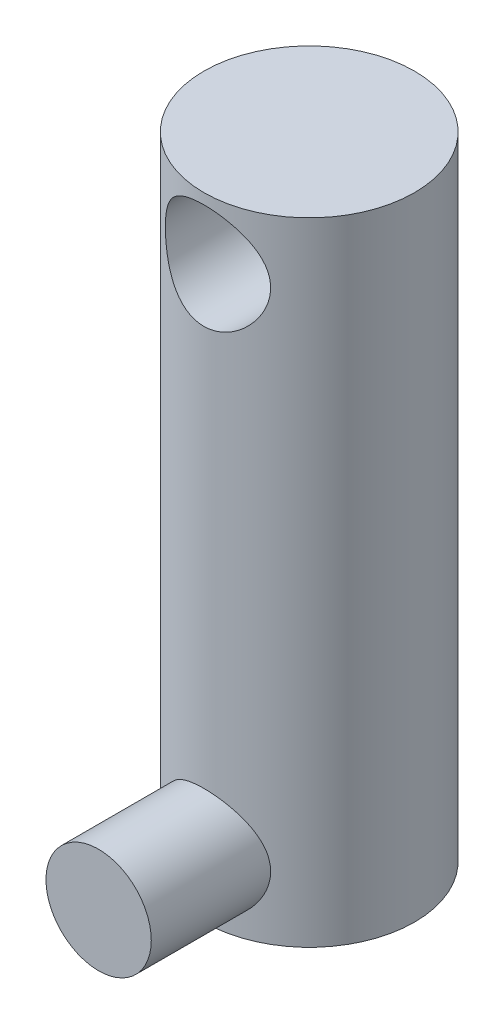
SolidWorks part; units mm, degrees
ref_plane "Front Plane" through (0, 0, 0) normal (0, 0, 1) x (1, 0, 0)
ref_plane "Top Plane" through (0, 0, 0) normal (0, 1, 0) x (1, 0, 0)
ref_plane "Right Plane" through (0, 0, 0) normal (1, 0, 0) x (0, 0, -1)
sketch "Sketch1" plane through (0, 0, 0) normal (0, 1, 0) x (1, 0, 0)
  circle A0 centre (0, 0) radius 5
  dimension "D1" = 10
extrude "Boss-Extrude1" add sketch "Sketch1" along normal blind 30
ref_plane "Plane1" through (0, 0, 5) normal (0, 0, 1) x (1, 0, 0)
sketch "Sketch2" plane through (0, 0, 5) normal (0, 0, 1) x (1, 0, 0)
  circle A0 centre (0, 3) radius 2.5
  point P2 (0, 0)
  point P8 (0, 0)
  point P9 (0, 25.9624)
  dimension "D1" = 5
  dimension "D2" = 3
extrude "Boss-Extrude2" add sketch "Sketch2" along normal blind 5 and the other way up to surface separate body other way up to face at (0, 30, 5)
sketch "Sketch3" plane through (0, 0, 0) normal (0, 0, 1) x (1, 0, 0)
  line L0 (5, 30) -> (-5, 30) construction
  circle A0 centre (0, 27) radius 2.5
  point P4 (0, 0)
  dimension "D1" = 5
  dimension "D2" = 3
extrude "Cut-Extrude1" cut sketch "Sketch3" along normal through all
